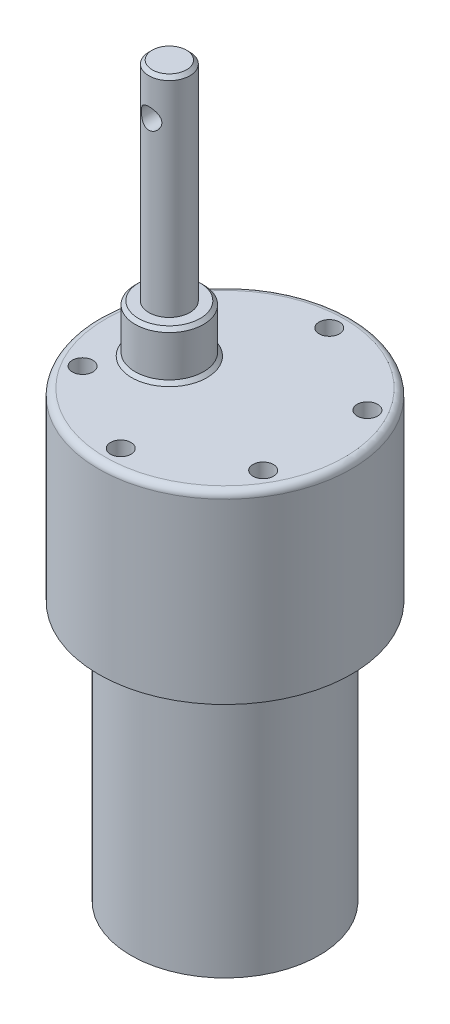
SolidWorks part; units mm, degrees
ref_plane "Front Plane" through (0, 0, 0) normal (0, 0, 1) x (1, 0, 0)
ref_plane "Top Plane" through (0, 0, 0) normal (0, 1, 0) x (1, 0, 0)
ref_plane "Right Plane" through (0, 0, 0) normal (1, 0, 0) x (0, 0, -1)
sketch "Sketch1" plane through (0, 0, 0) normal (0, 0, 1) x (1, 0, 0)
  line L0 (0, 116.3129) -> (0, 0) construction
  line L1 (0, 67) -> (18.5, 67)
  line L2 (18.5, 67) -> (18.5, 40)
  line L3 (18.5, 40) -> (13.75, 40)
  line L4 (13.75, 40) -> (13.75, 2)
  line L5 (13.75, 2) -> (4, 2)
  line L6 (4, 2) -> (4, 0)
  line L7 (4, 0) -> (0, 0)
  line L8 (0, 67) -> (0, 0)
  dimension "D1" = 27
  dimension "D2" = 40
  dimension "D3" = 37
  dimension "D4" = 27.5
  dimension "D5" = 38
  dimension "D6" = 4
revolve "Revolve1" add sketch "Sketch1" angle 360 about L0
sketch "Sketch2" plane through (0, 67, 0) normal (0, 1, 0) x (1, 0, 0)
  line L0 (0, 18.5) -> (0, -18.5) construction
  circle A0 centre (0, 0) radius 18.5 construction
  circle A1 centre (-8.1408, 0) radius 5
  dimension "D1" = 10
extrude "Boss-Extrude1" add sketch "Sketch2" along normal blind 7
sketch "Sketch3" plane through (0, 74, 0) normal (0, 1, 0) x (1, 0, 0)
  circle A0 centre (-8.1408, 0) radius 3
  dimension "D1" = 6
extrude "Boss-Extrude2" add sketch "Sketch3" along normal blind 30.5
sketch "Sketch4" plane through (0, 67, 0) normal (0, 1, 0) x (1, 0, 0)
  circle A0 centre (0, 0) radius 15.25 construction
  circle A1 centre (0, 15.25) radius 1.5
  circle A2 centre (13.2069, 7.625) radius 1.5
  circle A3 centre (13.2069, -7.625) radius 1.5
  circle A4 centre (0, -15.25) radius 1.5
  circle A5 centre (-13.2069, -7.625) radius 1.5
  circle A6 centre (-13.2069, 7.625) radius 1.5
  point P18 (0, 0)
  dimension "D1" = 30.5
  dimension "D2" = 3
  dimension "D3" = 6
extrude "Cut-Extrude1" cut sketch "Sketch4" against normal blind 3
sketch "Sketch5" plane through (0, 0, 0) normal (0, 0, 1) x (1, 0, 0)
  line L0 (-5.1408, 104.5) -> (-11.1408, 104.5) construction
  line L1 (-5.1408, 74) -> (-5.1408, 104.5) construction
  circle A0 centre (-8.1408, 98.6) radius 1.5
  dimension "D1" = 5.9
  dimension "D2" = 3
  dimension "D3" = 3
extrude "Cut-Extrude2" cut sketch "Sketch5" against normal blind 4 and the other way blind 4
chamfer "Chamfer1" distance 0.5 angle 45 2 edges at (-8.1408, 67, -5) (-8.1408, 74, 5)
fillet "Fillet1" radius 0.5 1 edges at (0, 0, 4)
chamfer "Chamfer2" distance 0.5 angle 45 1 edges at (0, 2, 4)
chamfer "Chamfer3" distance 0.5 angle 45 1 edges at (-8.1408, 104.5, 3)
fillet "Fillet4" radius 1 1 edges at (0, 67, 18.5)
sketch "Sketch6" plane through (0, 0, 0) normal (0, 0, 1) x (1, 0, 0)
  line L0 (13.7695, 40) -> (12.2695, 40)
  line L1 (-13.75, 40) -> (13.75, 40) construction
  line L2 (13.7695, 40) -> (13.7695, 38.5)
  arc A0 (13.7695, 38.5) -> (12.2695, 40) centre (12.2695, 38.5) ccw
  dimension "D1" = 1.5
revolve "Cut-Revolve1" cut sketch "Sketch6" angle 360 about L0
